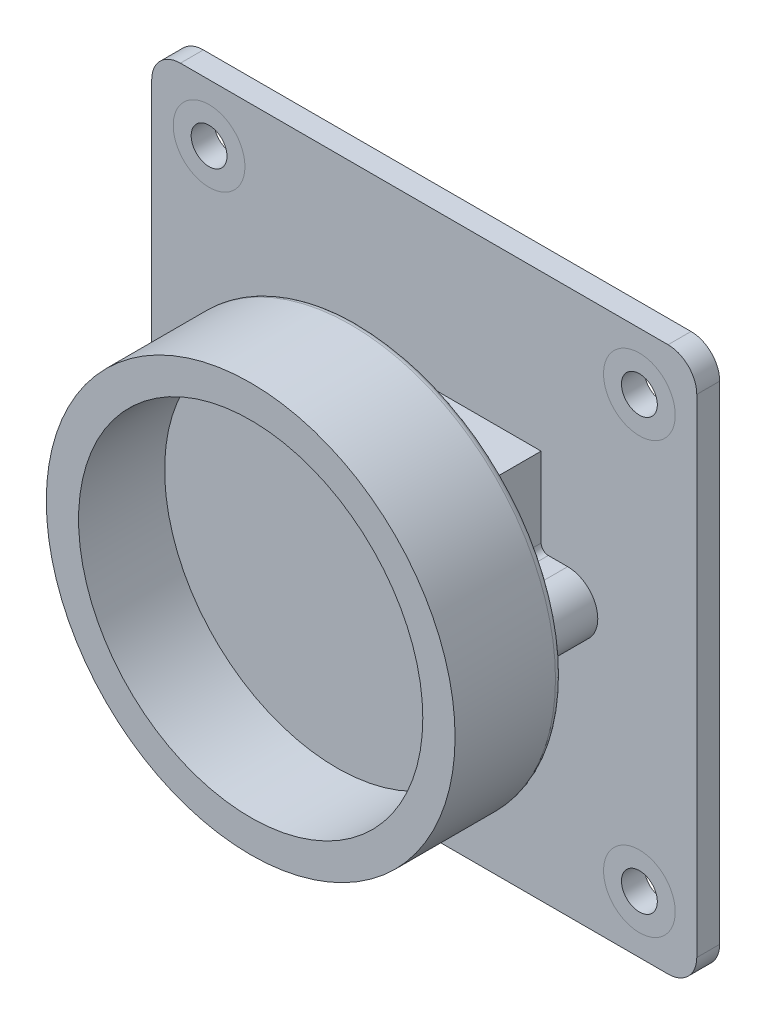
SolidWorks part; units mm, degrees
ref_plane "Front Plane" through (0, 0, 0) normal (0, 0, 1) x (1, 0, 0)
ref_plane "Top Plane" through (0, 0, 0) normal (0, 1, 0) x (1, 0, 0)
ref_plane "Right Plane" through (0, 0, 0) normal (1, 0, 0) x (0, 0, -1)
sketch "Sketch1" plane through (0, 0, 0) normal (0, 0, 1) x (1, 0, 0)
  line L1 (-19, 19) -> (19, 19)
  line L2 (-19, 19) -> (-19, -19)
  line L3 (-19, -19) -> (19, -19)
  line L4 (19, 19) -> (19, -19)
  line L5 (-19, 19) -> (19, -19) construction
  line L6 (-19, -19) -> (19, 19) construction
  point P0 (0, 0)
  dimension "D1" = 38
  dimension "D2" = 38
extrude "Boss-Extrude1" add sketch "Sketch1" along normal blind 1.6
sketch "Sketch2" plane through (0, 0, 1.6) normal (0, 0, 1) x (1, 0, 0)
  line L0 (0, 0) -> (-35355.3391, 35355.3391) construction
  line L1 (0, -1000) -> (0, 49000) construction
  line L2 (-1000, 0) -> (49000, 0) construction
  circle A0 centre (-15, 15) radius 1.25
  circle A1 centre (15, 15) radius 1.25
  circle A2 centre (15, -15) radius 1.25
  circle A3 centre (-15, -15) radius 1.25
  dimension "D1" = 2.5
  dimension "D2" = 30
extrude "Cut-Extrude1" cut sketch "Sketch2" against normal through all
fillet "Fillet1" radius 2 4 edges at (-19, -19, 0.8) (19, -19, 0.8) (19, 19, 0.8) (-19, 19, 0.8)
sketch "Sketch3" plane through (0, 0, 1.6) normal (0, 0, 1) x (1, 0, 0)
  line L0 (-1000, 0) -> (49000, 0) construction
  line L1 (0, -1000) -> (0, 49000) construction
  line L2 (-8.15, 8.15) -> (8.15, 8.15)
  line L3 (-8.15, 8.15) -> (-8.15, -8.15)
  line L4 (-8.15, -8.15) -> (8.15, -8.15)
  line L5 (8.15, 8.15) -> (8.15, -8.15)
  line L6 (-8.15, 8.15) -> (8.15, -8.15) construction
  line L7 (-8.15, -8.15) -> (8.15, 8.15) construction
  line L9 (-10, -2.1) -> (10, -2.1)
  line L10 (-10, -2.1) -> (-10, 2.1)
  line L11 (-10, 2.1) -> (10, 2.1)
  line L12 (10, -2.1) -> (10, 2.1)
  line L13 (-10, -2.1) -> (10, 2.1) construction
  line L14 (-10, 2.1) -> (10, -2.1) construction
  circle A0 centre (10, 0) radius 2.1
  circle A1 centre (-10, 0) radius 2.1
  point P1 (0, 0)
  point P14 (0, 0)
  dimension "D3" = 4.2
  dimension "D1" = 16.3
  dimension "D2" = 20
extrude "Boss-Extrude2" add sketch "Sketch3" along normal blind 4.6 separate body contours L3 L4 L5 L2 | L11 L12 L9 L10 | A1 | A0
sketch "Sketch4" plane through (0, 0, 6.2) normal (0, 0, 1) x (1, 0, 0)
  circle A0 centre (0, 0) radius 14.25
  dimension "D1" = 28.5
extrude "Boss-Extrude3" add sketch "Sketch4" along normal blind 7.5
sketch "Sketch5" plane through (0, 0, 13.7) normal (0, 0, 1) x (1, 0, 0)
  circle A1 centre (0, 0) radius 12
  dimension "D1" = 24
extrude "Cut-Extrude2" cut sketch "Sketch5" against normal blind 6
fillet "Fillet2" radius 0.5 5 edges at (-8.15, 2.1, 3.9) (-8.15, -2.1, 3.9) (8.15, -2.1, 3.9) (8.15, 2.1, 3.9) (14.25, 0, 6.2)
sketch "Sketch6" plane through (0, 0, 0) normal (0, 0, -1) x (-1, 0, 0)
  line L0 (0, -1000) -> (0, 49000) construction
  circle A0 centre (-10, 0) radius 1.75
  circle A1 centre (10, 0) radius 1.75
  dimension "D1" = 3.5
extrude "Boss-Extrude4" add sketch "Sketch6" along normal blind 1 separate body
fillet "Fillet3" radius 0.8 1 edges at (8.25, 0, -1)
fillet "Fillet4" radius 0.8 1 edges at (-8.25, 0, -1)
sketch "Sketch7" plane through (0, 0, 0) normal (0, 0, -1) x (-1, 0, 0)
  circle A0 centre (-15, 15) radius 2.5
  circle A1 centre (15, 15) radius 2.5
  circle A2 centre (15, -15) radius 2.5
  circle A3 centre (-15, -15) radius 2.5
  dimension "D1" = 5
split line "Split Line1"
